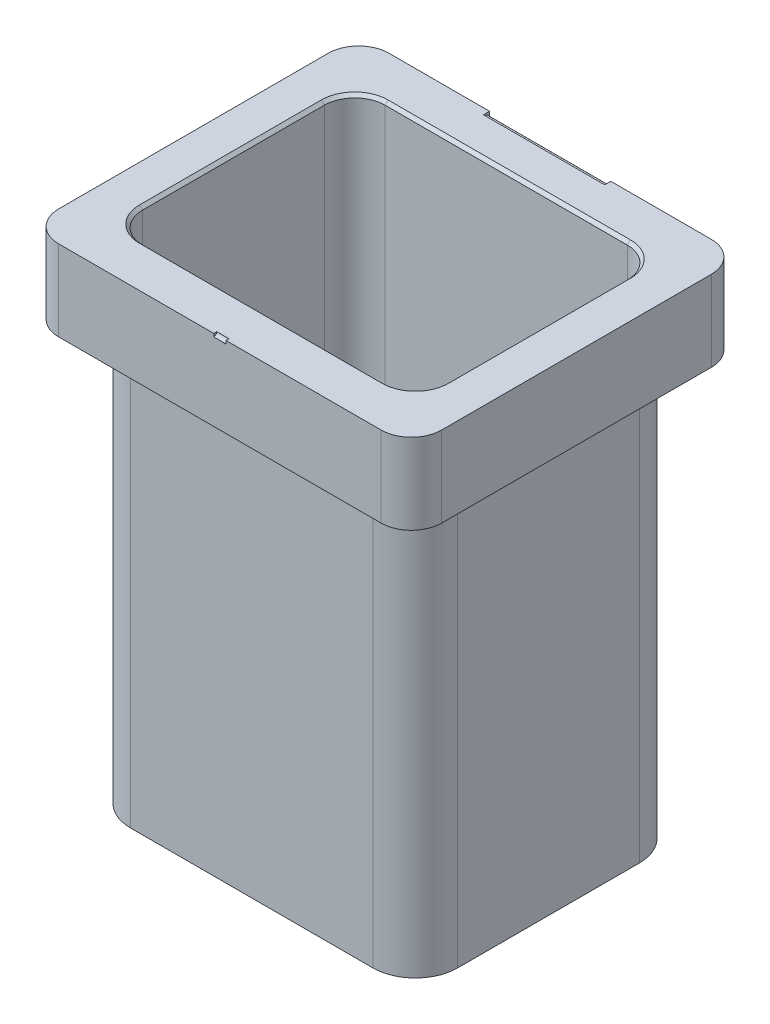
SolidWorks part; units mm, degrees
ref_plane "Front Plane" through (0, 0, 0) normal (0, 0, 1) x (1, 0, 0)
ref_plane "Top Plane" through (0, 0, 0) normal (0, 1, 0) x (1, 0, 0)
ref_plane "Right Plane" through (0, 0, 0) normal (1, 0, 0) x (0, 0, -1)
sketch "Sketch1" plane through (0, 0, 0) normal (0, 1, 0) x (1, 0, 0)
  line L1 (-200, 200) -> (200, 200)
  line L2 (-250, 150) -> (-250, -150)
  line L3 (-200, -200) -> (200, -200)
  line L4 (250, 150) -> (250, -150)
  line L5 (-250, 200) -> (250, -200) construction
  line L6 (-250, -200) -> (250, 200) construction
  arc A0 (-250, -150) -> (-200, -200) centre (-200, -150) ccw
  arc A1 (200, -200) -> (250, -150) centre (200, -150) ccw
  arc A2 (250, 150) -> (200, 200) centre (200, 150) ccw
  arc A3 (-200, 200) -> (-250, 150) centre (-200, 150) ccw
  point P0 (0, 0)
  dimension "D3" = 50
  dimension "D1" = 400
  dimension "D2" = 500
extrude "Boss-Extrude1" add sketch "Sketch1" along normal blind 800
shell "Shell1" thickness 20 removed face at (0, 800, 0) outward yes
fillet "Fillet1" radius 10 8 edges at (-235.3553, 800, 185.3553) (0, 800, 200) (235.3553, 800, 185.3553) (250, 800, 0) (235.3553, 800, -185.3553) (0, 800, -200) (-235.3553, 800, -185.3553) (-250, 800, 0)
sketch "Sketch2" plane through (0, 0, -220) normal (0, 0, -1) x (-1, 0, 0)
  line L0 (-200, 800) -> (200, 800) construction
  line L2 (-45.003, 800) -> (-45.003, 759.564)
  line L3 (-45.003, 759.564) -> (-15.003, 759.564)
  line L4 (45.003, 800) -> (45.003, 759.564)
  line L5 (14.997, 786.5249) -> (45.003, 759.564) construction
  line L6 (-45.003, 759.564) -> (-15.003, 786.5196) construction
  line L7 (-45.003, 800) -> (-15.003, 800)
  line L8 (-15.003, 800) -> (-15.003, 759.564)
  line L9 (14.997, 800) -> (14.997, 759.564)
  line L10 (14.997, 759.564) -> (45.003, 759.564)
  line L11 (14.997, 800) -> (45.003, 800)
  point P0 (0, 800)
  dimension "D1" = 30
  dimension "D2" = 30
extrude "Boss-Extrude2" add sketch "Sketch2" along normal blind 50
sketch "Sketch3" plane through (45.003, 0, 0) normal (1, 0, 0) x (0, 0, -1)
  line L0 (245, 800) -> (270, 800)
  line L1 (270, 800) -> (270, 759.564)
  line L2 (270, 759.564) -> (245, 759.564)
  circle A0 centre (245, 779.782) radius 10
  arc A1 (245, 759.564) -> (245, 800) centre (245, 779.782) ccw
extrude "Cut-Extrude1" cut sketch "Sketch3" against normal blind 91
sketch "Sketch4" plane through (0, 0, -220) normal (0, 0, -1) x (-1, 0, 0)
  line L1 (-115.6138, 794.6334) -> (-59.6966, 794.6334)
  line L2 (-115.6138, 794.6334) -> (-115.6138, 764.9307)
  line L3 (-115.6138, 764.9307) -> (-59.6966, 764.9307)
  line L4 (-59.6966, 794.6334) -> (-59.6966, 764.9307)
  line L5 (-115.6138, 794.6334) -> (-59.6966, 764.9307) construction
  line L6 (-115.6138, 764.9307) -> (-59.6966, 794.6334) construction
  point P0 (-87.6552, 779.782)
extrude "Boss-Extrude3" add sketch "Sketch4" along normal blind 46
sketch "Sketch5" plane through (59.6966, 0, 0) normal (-1, 0, 0) x (0, 0, 1)
  circle A0 centre (-245, 779.782) radius 7.9634
  circle A1 centre (-245, 779.782) radius 2.2381
extrude "Boss-Extrude4" add sketch "Sketch5" along normal blind 105
chamfer "Chamfer1" distance 5 angle 45 2 edges at (87.6552, 764.9307, -266) (87.6552, 794.6334, -266)
sketch "Sketch8" plane through (0, 800, 0) normal (0, 1, 0) x (1, 0, 0)
  line L1 (-266, 272.5) -> (266, 272.5)
  line L2 (-316, 222.5) -> (-316, -222.5)
  line L3 (-266, -272.5) -> (266, -272.5)
  line L4 (316, 222.5) -> (316, -222.5)
  line L5 (-316, 272.5) -> (316, -272.5) construction
  line L6 (-316, -272.5) -> (316, 272.5) construction
  arc A0 (-316, -222.5) -> (-266, -272.5) centre (-266, -222.5) ccw
  arc A1 (266, -272.5) -> (316, -222.5) centre (266, -222.5) ccw
  arc A2 (316, 222.5) -> (266, 272.5) centre (266, 222.5) ccw
  arc A3 (-266, 272.5) -> (-316, 222.5) centre (-266, 222.5) ccw
  point P0 (0, 0)
  dimension "D1" = 50
  dimension "D2" = 632
  dimension "D3" = 545
extrude "Boss-Extrude5" add sketch "Sketch8" against normal blind 125 and the other way blind 8
sketch "Sketch10" plane through (0, 808, 0) normal (0, 1, 0) x (1, 0, 0)
  line L1 (-200, -220) -> (200, -220)
  line L2 (-270, -150) -> (-270, 150)
  line L3 (-200, 220) -> (200, 220)
  line L4 (270, -150) -> (270, 150)
  line L5 (-270, -220) -> (270, 220) construction
  line L6 (-270, 220) -> (270, -220) construction
  arc A0 (-270, 150) -> (-200, 220) centre (-200, 150) cw
  arc A1 (200, 220) -> (270, 150) centre (200, 150) cw
  arc A2 (270, -150) -> (200, -220) centre (200, -150) cw
  arc A3 (-200, -220) -> (-270, -150) centre (-200, -150) cw
  point P0 (0, 0)
  dimension "D1" = 70
sketch "Sketch11" plane through (0, 808, 0) normal (0, 1, 0) x (1, 0, 0)
  line L1 (-200, -200) -> (200, -200)
  line L2 (-250, -150) -> (-250, 150)
  line L3 (-200, 200) -> (200, 200)
  line L4 (250, -150) -> (250, 150)
  line L5 (-250, -200) -> (250, 200) construction
  line L6 (-250, 200) -> (250, -200) construction
  arc A0 (-250, 150) -> (-200, 200) centre (-200, 150) cw
  arc A1 (200, 200) -> (250, 150) centre (200, 150) cw
  arc A2 (250, -150) -> (200, -200) centre (200, -150) cw
  arc A3 (-200, -200) -> (-250, -150) centre (-200, -150) cw
  point P0 (0, 0)
  dimension "D1" = 50
extrude "Cut-Extrude5" cut sketch "Sketch11" against normal up to next
sketch "Sketch12" plane through (0, 0, 0) normal (1, 0, 0) x (0, 0, -1)
  circle A0 centre (50, 50) radius 15
sketch "Sketch13" plane through (0, 0, 0) normal (1, 0, 0) x (0, 0, -1)
  circle A0 centre (267.5, 803) radius 7.0907
extrude "Cut-Extrude8" cut sketch "Sketch13" against normal blind 100 and the other way blind 100
sketch "Sketch15" plane through (0, 0, 0) normal (1, 0, 0) x (0, 0, -1)
  circle A0 centre (267.5, 803) radius 1.9889
extrude "Boss-Extrude6" add sketch "Sketch15" along normal up to next and the other way up to next separate body
sketch "Sketch16" plane through (0, 0, 0) normal (1, 0, 0) x (0, 0, -1)
  circle A0 centre (-272.5, 808) radius 5
extrude "Cut-Extrude9" cut sketch "Sketch16" against normal blind 10 and the other way blind 10
chamfer "Chamfer2" distance 5 angle 45 8 edges at (-235.3553, 808, 185.3553) (0, 808, 200) (235.3553, 808, 185.3553) (250, 808, 0) (235.3553, 808, -185.3553) (0, 808, -200) (-235.3553, 808, -185.3553) (-250, 808, 0)
